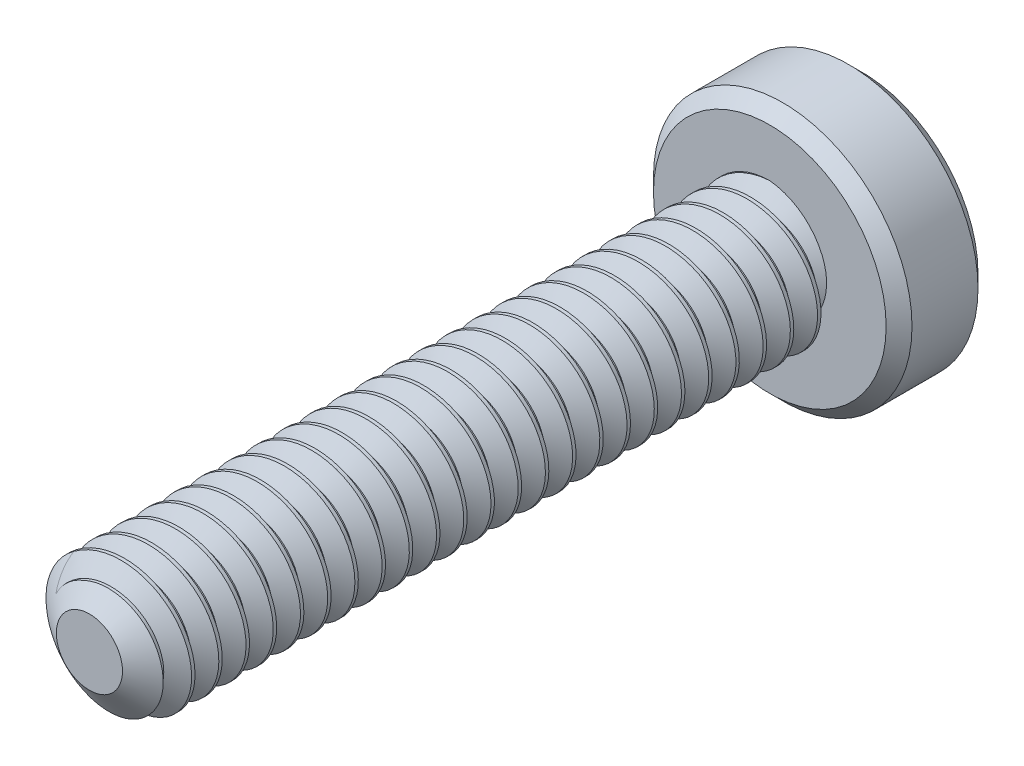
SolidWorks part; units mm, degrees
other "DetailItem1"
material "18-8 Stainless Steel"
ref_plane "Front Plane" through (0, 0, 0) normal (0, 0, 1) x (1, 0, 0)
ref_plane "Top Plane" through (0, 0, 0) normal (0, 1, 0) x (1, 0, 0)
ref_plane "Right Plane" through (0, 0, 0) normal (1, 0, 0) x (0, 0, -1)
sketch "Sketch1" plane through (0, 0, 0) normal (0, 0, 1) x (1, 0, 0)
  circle A0 centre (0, 0) radius 1
  dimension "OD" = 2
extrude "Extrude1" add sketch "Sketch1" against normal blind 10
sketch "Sketch2" plane through (0, 0, 0) normal (0, 0, 1) x (1, 0, 0)
  circle A0 centre (0, 0) radius 1 construction
  circle A1 centre (0, 0) radius 1
curve "Helix/Spiral1" pitch 0.4 height 10.4 radius 1 centre (0, 0, 0) axis (0, 0, -1) start towards (0, 1, 0) parameters "pitch"=0.4
sketch "Sketch3" plane through (0, 0, 0) normal (1, 0, 0) x (0, 0, -1)
  line L0 (-0.35, 1) -> (-0.2, 0.7402)
  line L1 (-0.2, 0.7402) -> (-0.15, 0.7402)
  line L2 (-0.15, 0.7402) -> (0, 1)
  line L3 (-0.35, 1) -> (0, 1)
  line L4 (-0.175, 1) -> (-0.175, 0.7402) construction
  line L5 (-0.275, 0.8701) -> (-0.075, 0.8701) construction
  line L6 (0, 1) -> (0, -1) construction
  dimension "D1" = 0.05
  dimension "D2" = 0.2
  dimension "D3" = 60
sweep "Cut-Sweep1" cut profiles "Sketch3" path "Helix/Spiral1" align with end faces yes
sketch "Sketch4" plane through (0, 0, 0) normal (1, 0, 0) x (0, 0, -1)
  line L0 (0.3598, 1) -> (0, 0.4862)
  line L1 (0, 0.4862) -> (0, 1)
  line L2 (0.3598, 1) -> (0, 1)
  line L3 (-0.35, 1) -> (0, 1) construction
  line L4 (0, 0) -> (7.0209, 0) construction
  dimension "D1" = 55
  dimension "D2" = 0.254
revolve "Cut-Revolve1" cut sketch "Sketch4" angle 360 about L4
sketch "Sketch6" plane through (0, 0, -10) normal (0, 0, -1) x (-1, 0, 0)
  circle A0 centre (0, 0) radius 1.9
  dimension "head dia" = 3.8
extrude "Extrude2" add sketch "Sketch6" along normal blind 1.35
sketch "Sketch7" plane through (0, 0, -11.35) normal (0, 0, -1) x (-1, 0, 0)
  line L1 (0, 0.7506) -> (-0.65, 0.3753)
  line L2 (-0.65, 0.3753) -> (-0.65, -0.3753)
  line L3 (-0.65, -0.3753) -> (0, -0.7506)
  line L4 (0, -0.7506) -> (0.65, -0.3753)
  line L5 (0.65, -0.3753) -> (0.65, 0.3753)
  line L6 (0.65, 0.3753) -> (0, 0.7506)
  circle A0 centre (0, 0) radius 0.65 construction
  dimension "hex dia" = 1.3
extrude "Cut-Extrude1" cut sketch "Sketch7" against normal blind 0.975
sketch "Sketch8" plane through (0, 0, -11.35) normal (0, 0, -1) x (-1, 0, 0)
  circle A0 centre (0, 0) radius 0.7506
extrude "Cut-Extrude2" cut sketch "Sketch8" against normal through all draft 45
chamfer "Chamfer1" distance 0.19 angle 45 2 edges at (-1.9, 0, -11.35) (-1.9, 0, -10)
sketch "Sketch10" plane through (0, 0, -10) normal (0, 0, 1) x (1, 0, 0)
  circle A1 centre (0, 0) radius 1
  circle A2 centre (0, 0) radius 1
  dimension "D1" = 0
ref_plane "Plane1" through (0, 0, -30) normal (0, 0, 1) x (1, 0, 0)
extrude "partial thread" [suppressed] add sketch "Sketch10" along normal up to surface (10 mm away) separate body
chamfer "Chamfer2" [suppressed] distance 0.04 angle 45
combine bodies "Combine1" [suppressed] operation type add bodies to combine 107 108
sketch "Sketch9" plane through (0, 0, 0) normal (1, 0, 0) x (0, 0, -1)
  line L0 (0, 1) -> (0, -1) construction
  line L1 (1, 1) -> (1, -1) construction
  dimension "D1" = 1
equation "\"D3@Helix/Spiral1\" = \"screw length@Extrude1\"+\"pitch@Helix/Spiral1\""
equation "\"D1@Sketch3\" = \"pitch@Helix/Spiral1\"*.125"
equation "\"D2@Sketch3\" = \"pitch@Helix/Spiral1\"*.5"
equation "\"D1@Cut-Extrude1\" = \"hex dia@Sketch7\"*.75"
equation "\"D1@Chamfer1\" = \"head dia@Sketch6\"*.05"
equation "\"D1@Sketch9\" = \"pitch@Helix/Spiral1\"*2.5"
equation "\"D1@Chamfer2\"=\"OD@Sketch1\"*.02"
